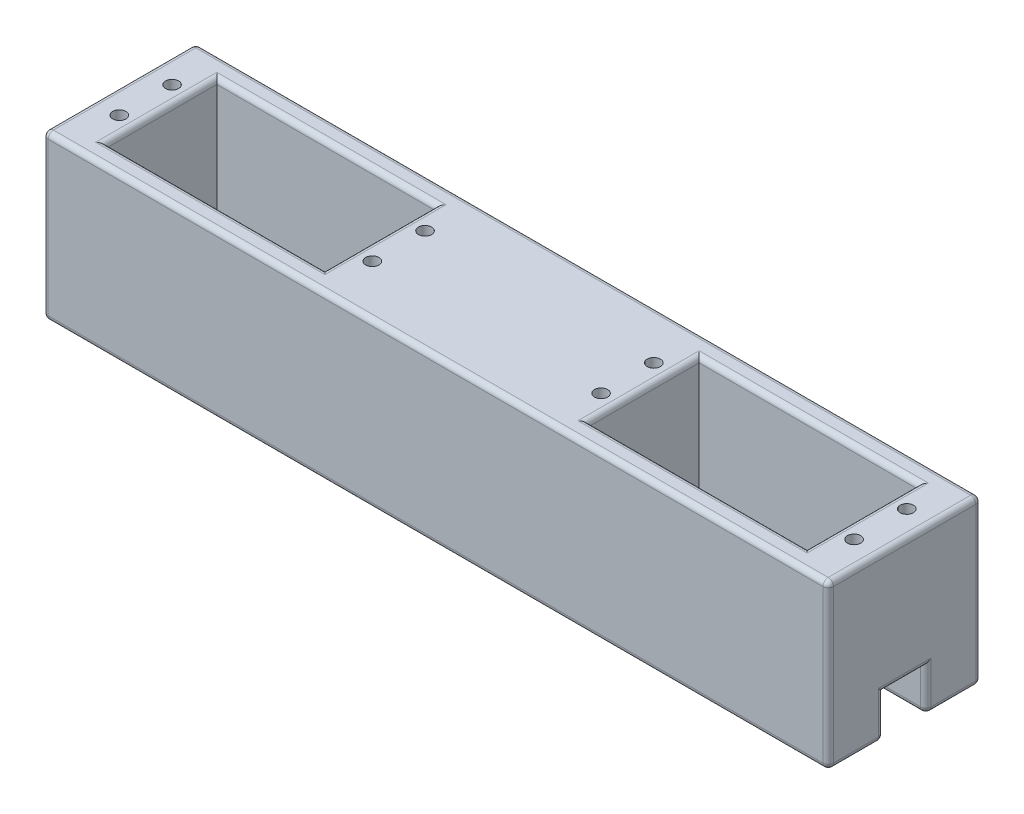
SolidWorks part; units mm, degrees
material "ABS"
ref_plane "前视基准面" through (0, 0, 0) normal (0, 0, 1) x (1, 0, 0)
ref_plane "上视基准面" through (0, 0, 0) normal (0, 1, 0) x (1, 0, 0)
ref_plane "右视基准面" through (0, 0, 0) normal (1, 0, 0) x (0, 0, -1)
sketch "草图1" plane through (0, 0, 0) normal (0, 1, 0) x (1, 0, 0)
  line L1 (74.5, -14.5) -> (-74.5, -14.5)
  line L2 (74.5, -14.5) -> (74.5, 14.5)
  line L3 (74.5, 14.5) -> (-74.5, 14.5)
  line L4 (-74.5, -14.5) -> (-74.5, 14.5)
  line L5 (74.5, -14.5) -> (-74.5, 14.5) construction
  line L6 (74.5, 14.5) -> (-74.5, -14.5) construction
  line L7 (-66.5, -10.5) -> (-25, -10.5)
  line L8 (-66.5, -10.5) -> (-66.5, 10.5)
  line L9 (-66.5, 10.5) -> (-25, 10.5)
  line L10 (-25, -10.5) -> (-25, 10.5)
  line L11 (25, -10.5) -> (66.5, -10.5)
  line L12 (25, -10.5) -> (25, 10.5)
  line L13 (25, 10.5) -> (66.5, 10.5)
  line L14 (66.5, -10.5) -> (66.5, 10.5)
  point P0 (0, 0)
  dimension "D1" = 29
  dimension "D2" = 41.5
  dimension "D3" = 8
  dimension "D4" = 4
  dimension "D5" = 4
  dimension "D6" = 41.5
  dimension "D7" = 50
  dimension "D8" = 8
  dimension "D9" = 4
  dimension "D10" = 4
extrude "凸台-拉伸1" add sketch "草图1" along normal blind 28
sketch "草图2" plane through (0, 0, 0) normal (0, -1, 0) x (1, 0, 0)
  line L1 (-74.5, 14.5) -> (74.5, 14.5)
  line L2 (-74.5, 14.5) -> (-74.5, -14.5)
  line L3 (-74.5, -14.5) -> (74.5, -14.5)
  line L4 (74.5, 14.5) -> (74.5, -14.5)
extrude "凸台-拉伸2" add sketch "草图2" along normal blind 3
sketch "草图3" plane through (74.5, 0, 0) normal (1, 0, 0) x (0, 0, -1)
  line L0 (14.5, -3) -> (-14.5, -3) construction
  line L1 (-4, -3) -> (4, -3)
  line L2 (-4, -3) -> (-4, 5)
  line L3 (-4, 5) -> (4, 5)
  line L4 (4, -3) -> (4, 5)
  point P6 (0, -3)
  dimension "D1" = 8
  dimension "D2" = 8
extrude "切除-拉伸1" cut sketch "草图3" against normal blind 8
sketch "草图4" plane through (0, -3, 0) normal (0, -1, 0) x (-1, 0, 0)
  line L0 (0, 0) -> (0, -50000) construction
  line L1 (-25, 10.5) -> (-25, -10.5) construction
  circle A0 centre (-56.2, 0) radius 5.5
  circle A1 centre (56.2, 0) radius 5.5
  dimension "D2" = 11
  dimension "D1" = 31.2
mirror "镜向1" about plane through (0, 0, 0) normal (1, 0, 0) of "切除-拉伸1"
extrude "凸台-拉伸3" add sketch "草图4" along normal blind 8
fillet "圆角1" radius 1 2 edges at (-56.2, -11, 5.5) (56.2, -11, -5.5)
fillet "圆角5" radius 1 28 edges at (66.5, 28, 0) (45.75, 28, -10.5) (25, 28, 0) (45.75, 28, 10.5) (-25, 28, 0) (-45.75, 28, -10.5) (-66.5, 28, 0) (-45.75, 28, 10.5) (74.5, 28, 0) (74.5, -3, -9.25) (74.5, 1, -4) (74.5, 5, 0) (74.5, 1, 4) (74.5, -3, 9.25) (0, 28, 14.5) (74.5, 12.5, 14.5) (0, -3, 14.5) (-74.5, 5, 0) (-74.5, 1, -4) (-74.5, -3, -9.25) (-74.5, 28, 0) (-74.5, 12.5, 14.5) (-74.5, -3, 9.25) (-74.5, 1, 4) (0, 28, -14.5) (-74.5, 12.5, -14.5) (0, -3, -14.5) (74.5, 12.5, -14.5)
fillet "圆角6" radius 1 12 edges at (74.2071, -2.7071, 4.2929) (74.2071, -2.7071, -4.2929) (-74.2071, -2.7071, 4.2929) (-74.2071, -2.7071, -4.2929) (-66.5, 0, 0) (66.5, 0, 0) (70, -3, 4) (70, -3, -4) (66.5, -3, 0) (-70, -3, 4) (-70, -3, -4) (-66.5, -3, 0)
sketch "草图5" plane through (0, 28, 0) normal (0, 1, 0) x (1, 0, 0)
  line L0 (0, 0) -> (0, 12.1068) construction
  line L1 (-73.5, 14.5) -> (73.5, 14.5) construction
  line L2 (73.5, -14.5) -> (-73.5, -14.5) construction
  line L3 (74.5, 13.5) -> (74.5, -13.5) construction
  circle A0 centre (-69.7, 5.2) radius 1.25
  circle A1 centre (-69.7, -4.8) radius 1.25
  circle A2 centre (-21.7, 5.2) radius 1.25
  circle A3 centre (-21.7, -4.8) radius 1.25
  circle A4 centre (21.7, -4.8) radius 1.25
  circle A5 centre (21.7, 5.2) radius 1.25
  circle A6 centre (69.7, -4.8) radius 1.25
  circle A7 centre (69.7, 5.2) radius 1.25
  dimension "D1" = 2.5
  dimension "D2" = 21.7
  dimension "D3" = 9.3
  dimension "D4" = 9.7
  dimension "D5" = 4.8
extrude "切除-拉伸2" cut sketch "草图5" against normal blind 8
